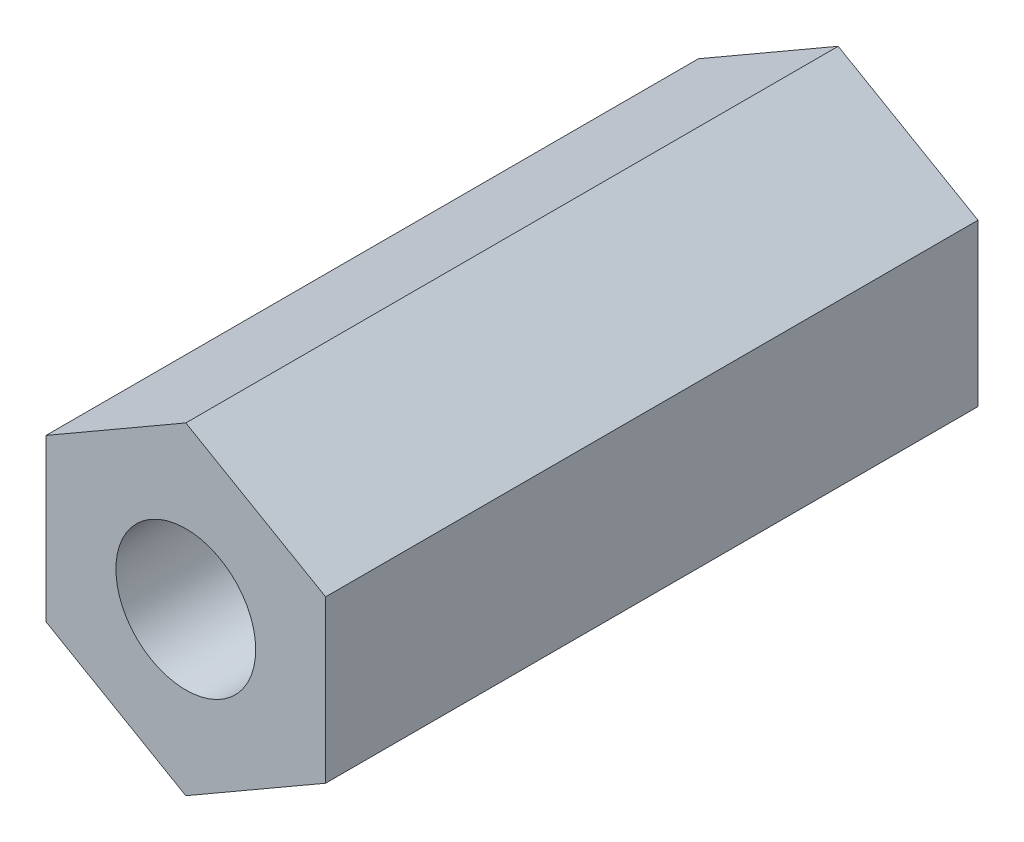
SolidWorks part; units mm, degrees
ref_plane "Front Plane" through (0, 0, 0) normal (0, 0, 1) x (1, 0, 0)
ref_plane "Top Plane" through (0, 0, 0) normal (0, 1, 0) x (1, 0, 0)
ref_plane "Right Plane" through (0, 0, 0) normal (1, 0, 0) x (0, 0, -1)
sketch "Sketch3" plane through (0, 0, 0) normal (1, 0, 0) x (0, 0, -1)
  line L0 (-7, 0) -> (7, 0) construction
  line L1 (0, 3) -> (0, -3) construction
  line L2 (-7, 1.5) -> (-7, -1.5) construction
  point P2 (2.2, 0)
  point P3 (-2.2, 0)
  dimension "Length" = 14
  dimension "Min Thread Length" = 4.8
  dimension "D1" = 4.8
  dimension "Thread Dia" = 3
  dimension "Hex" = 6
sketch "Sketch1" plane through (0, 0, 0) normal (0, 0, 1) x (1, 0, 0)
  line L1 (0, 3.4641) -> (-3, 1.7321)
  line L2 (-3, 1.7321) -> (-3, -1.7321)
  line L3 (-3, -1.7321) -> (0, -3.4641)
  line L4 (0, -3.4641) -> (3, -1.7321)
  line L5 (3, -1.7321) -> (3, 1.7321)
  line L6 (3, 1.7321) -> (0, 3.4641)
  circle A0 centre (0, 0) radius 3 construction
  circle A1 centre (0, 0) radius 1.5
extrude "Extrude1" add sketch "Sketch1" along normal up to vertex (7 mm away) and the other way up to vertex (7 mm away) up to point (0, 0, 7) other way up to point (0, 0, -7)
sketch "Sketch11" plane through (0, 0, -7) normal (0, 0, -1) x (-1, 0, 0)
  circle A0 centre (0, 0) radius 1.5 construction
  circle A1 centre (0, 0) radius 1.5
curve "Helix/Spiral1" [suppressed] pitch 0.5 height 14.5 turns 29 parameters "Pitch"=0.5
sketch "Sketch12" plane through (0, 0, 0) normal (1, 0, 0) x (0, 0, -1)
  line L0 (7.4375, 1.5) -> (7, 1.5)
  line L1 (7.4375, 1.5) -> (7.25, 1.1752)
  line L2 (7.25, 1.1752) -> (7.1875, 1.1752)
  line L3 (7.1875, 1.1752) -> (7, 1.5)
  line L4 (7.2188, 1.1752) -> (7.2188, 1.5) construction
  line L5 (7.3438, 1.3376) -> (7.0938, 1.3376) construction
  dimension "D1" = 0.0625
  dimension "D2" = 0.25
  dimension "D3" = 60
sweep "Sweep1" [suppressed] add profiles "Sketch12" path "Helix/Spiral1"
sketch "Sketch6" plane through (0, 0, -7) normal (0, 0, -1) x (-1, 0, 0)
  line L6 (0, 3.4641) -> (-3, 1.7321)
  line L7 (-3, 1.7321) -> (-3, -1.7321)
  line L8 (-3, -1.7321) -> (0, -3.4641)
  line L9 (0, -3.4641) -> (3, -1.7321)
  line L10 (3, -1.7321) -> (3, 1.7321)
  line L11 (3, 1.7321) -> (0, 3.4641)
  line L12 (0, 3.4641) -> (-3, 1.7321)
  line L13 (-3, 1.7321) -> (-3, -1.7321)
  line L14 (-3, -1.7321) -> (0, -3.4641)
  line L15 (0, -3.4641) -> (3, -1.7321)
  line L16 (3, -1.7321) -> (3, 1.7321)
  line L17 (3, 1.7321) -> (0, 3.4641)
  dimension "D1" = 0
extrude "Extrude2" [suppressed] cut sketch "Sketch6" along normal through all
sketch "Sketch7" plane through (0, 0, -7) normal (0, 0, -1) x (-1, 0, 0)
  circle A2 centre (0, 0) radius 1.5508
  circle A3 centre (0, 0) radius 1.5508
  dimension "D1" = 0.0508
extrude "Extrude3" [suppressed] cut sketch "Sketch7" against normal through all draft 43
sketch "Sketch8" plane through (0, 0, -7) normal (0, 0, -1) x (-1, 0, 0)
  circle A0 centre (0, 0) radius 3 construction
  circle A1 centre (0, 0) radius 3
extrude "Extrude4" [suppressed] cut sketch "Sketch8" against normal through all draft 60 flip side to cut
mirror "Mirror1" [suppressed] about plane through (0, 0, 0) normal (0, 0, 1)
sketch "Sketch9" [suppressed] plane through (0, 0, 0) normal (1, 0, 0) x (0, 0, -1)
  line L1 (-1.2, 1.1353) -> (1.2, 1.1353)
  line L2 (-1.2, 1.1353) -> (-1.2, 0)
  line L3 (-1.2, 0) -> (1.2, 0)
  line L4 (1.2, 1.1353) -> (1.2, 0)
  line L7 (-6, 0) -> (6, 0) construction
revolve "Revolve" [suppressed] add sketch "Sketch9" angle 360 about L0
sketch "Sketch10" [suppressed] plane through (0, 0, 0) normal (1, 0, 0) x (0, 0, -1)
  line L0 (6, 1.25) -> (1.2, 1.25)
  line L1 (-6, 1.25) -> (-1.2, 1.25)
  line L2 (1.2, 1.25) -> (1.2, -1.25)
  line L3 (-6, -1.25) -> (-1.2, -1.25)
  line L4 (-1.2, 1.25) -> (-1.2, -1.25)
  line L5 (1.2, -1.25) -> (6, -1.25)
equation "\"D1@Sketch3\" = \"Min Thread Length@Sketch3\""
equation "\"D3@Helix/Spiral1\" = \"Length@Sketch3\"+\"Pitch@Helix/Spiral1\""
equation "\"D1@Sketch12\" = \"Pitch@Helix/Spiral1\"*.125"
equation "\"D2@Sketch12\" = \"Pitch@Helix/Spiral1\"*.5"
